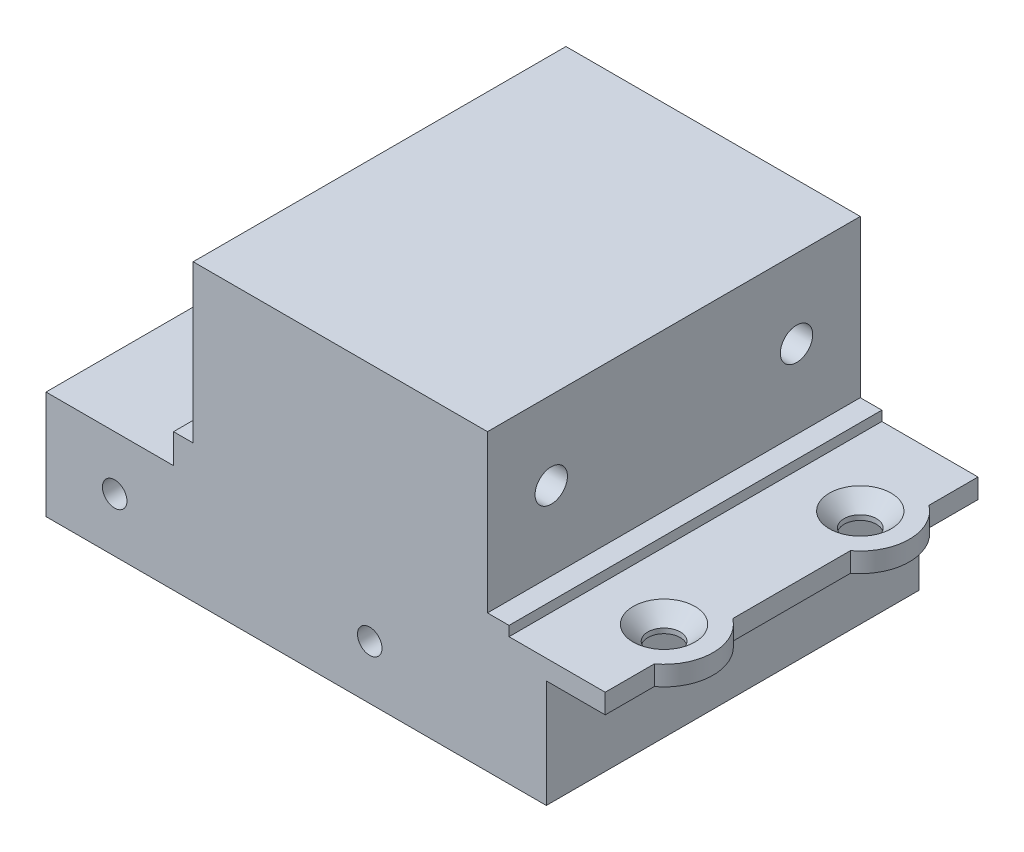
SolidWorks part; units mm, degrees
ref_plane "Спереди" through (0, 0, 0) normal (0, 0, 1) x (1, 0, 0)
ref_plane "Сверху" through (0, 0, 0) normal (0, 1, 0) x (1, 0, 0)
ref_plane "Справа" through (0, 0, 0) normal (1, 0, 0) x (0, 0, -1)
sketch "Эскиз6" [suppressed] plane through (0, 0, 0) normal (0, 1, 0) x (1, 0, 0)
  line L0 (-20, 0) -> (31, 0) construction
  line L1 (-20, -19) -> (31, -19)
  line L2 (-20, -19) -> (-20, 19)
  line L3 (-20, 19) -> (31, 19)
  line L4 (31, -19) -> (31, 19)
  line L5 (0, -19) -> (0, 19) construction
  dimension "D1" = 31
  dimension "D2" = 20
  dimension "D3" = 38
extrude "тело" [suppressed] add sketch "Эскиз6" along normal blind 11
sketch "Эскиз10" [suppressed] plane through (0, 11, 0) normal (0, 1, 0) x (1, 0, 0)
  circle A0 centre (0, 0) radius 10
  dimension "D1" = 20
extrude "основание оси" [suppressed] add sketch "Эскиз10" along normal blind 3
fillet "Скругление1" [suppressed] radius 3
sketch "Эскиз13" [suppressed] plane through (0, 0, 19) normal (0, 0, 1) x (1, 0, 0)
  line L0 (31, 5.5) -> (-13, 5.5) construction
  line L1 (31, 11) -> (31, 0) construction
  line L2 (0, 0) -> (0, 11) construction
  line L3 (-20, 11) -> (31, 11) construction
  circle A0 centre (-13, 5.5) radius 1.25
  circle A1 centre (13, 5.5) radius 1.25
  dimension "D1" = 2.5
  dimension "D2" = 26
  dimension "D3" = 18
extrude "отверстия под шурупы" [suppressed] cut sketch "Эскиз13" against normal through all
sketch "Эскиз15" [suppressed] plane through (0, 14, 0) normal (0, 1, 0) x (1, 0, 0)
  circle A0 centre (0, 0) radius 8.65
  dimension "D1" = 17.3
extrude "ось" [suppressed] add sketch "Эскиз15" along normal blind 13
sketch "Эскиз16" [suppressed] plane through (0, 27, 0) normal (0, 1, 0) x (1, 0, 0)
  line L0 (-7, 1.65) -> (-8.4912, 1.65) construction
  line L1 (-7, -1.65) -> (-8.4912, -1.65) construction
  line L2 (-1.65, 7) -> (-1.65, 8.4912)
  line L3 (1.65, 7) -> (1.65, 8.4912)
  line L4 (7, 1.65) -> (8.4912, 1.65) construction
  line L5 (7, -1.65) -> (8.4912, -1.65) construction
  line L6 (1.65, -7) -> (1.65, -8.4912)
  line L8 (-1.65, -7) -> (-1.65, -8.4912)
  circle A0 centre (0, 0) radius 7 construction
  arc A1 (-1.65, 7) -> (1.65, 7) centre (0, 7) ccw
  arc A2 (7, 1.65) -> (7, -1.65) centre (7, 0) ccw construction
  arc A3 (1.65, -7) -> (-1.65, -7) centre (0, -7) ccw
  arc A4 (-7, -1.65) -> (-7, 1.65) centre (-7, 0) ccw construction
  arc A5 (-8.4912, 1.65) -> (-8.4912, -1.65) centre (0, 0) ccw construction
  circle A6 centre (0, 0) radius 8.65 construction
  arc A7 (1.65, 8.4912) -> (-1.65, 8.4912) centre (0, 0) ccw
  arc A8 (8.4912, -1.65) -> (8.4912, 1.65) centre (0, 0) ccw construction
  arc A9 (-1.65, -8.4912) -> (1.65, -8.4912) centre (0, 0) ccw
  dimension "D1" = 14
  dimension "D2" = 1.65
extrude "крепление к серве" [suppressed] cut sketch "Эскиз16" against normal up to surface (13 mm away)
sketch "Эскиз26" [suppressed] plane through (0, 14, 0) normal (0, 1, 0) x (1, 0, 0)
  circle A0 centre (0, 7) radius 1.65
  circle A1 centre (0, -7) radius 1.65
  arc A2 (1.65, -7) -> (-1.65, -7) centre (0, -7) ccw construction
extrude "продолжение креплений" [suppressed] cut sketch "Эскиз26" against normal through all
chamfer "Фаска7" [suppressed] distance 2 angle 45
sketch "Эскиз17" [suppressed] plane through (0, 27, 0) normal (0, 1, 0) x (1, 0, 0)
  circle A0 centre (0, 0) radius 3
  dimension "D1" = 6
extrude "отверстие под болтик" [suppressed] cut sketch "Эскиз17" against normal through all
sketch "Эскиз24" [suppressed] plane through (0, 11, 0) normal (0, 1, 0) x (1, 0, 0)
  line L0 (31, 19) -> (-20, 19) construction
  line L1 (-15, 19) -> (15, 19)
  line L2 (-15, 19) -> (-15, -19)
  line L3 (-15, -19) -> (15, -19)
  line L4 (15, 19) -> (15, -19)
  line L5 (-20, -19) -> (31, -19) construction
  line L6 (0, 19) -> (0, -19) construction
  dimension "D1" = 30
extrude "крепление к арке" [suppressed] add sketch "Эскиз24" along normal blind 15
sketch "Эскиз27" [suppressed] plane through (-15, 0, 0) normal (-1, 0, 0) x (0, 0, 1)
  line L0 (0, 11) -> (0, 26) construction
  line L1 (-19, 11) -> (19, 11) construction
  line L2 (-19, 26) -> (19, 26) construction
  line L3 (-12.5, 18.5) -> (12.5, 18.5) construction
  circle A0 centre (-12.5, 18.5) radius 1.65
  circle A1 centre (12.5, 18.5) radius 1.65
  dimension "D2" = 3.3
  dimension "D1" = 25
  dimension "D3" = 7.5
extrude "отверстия под болты" [suppressed] cut sketch "Эскиз27" against normal through all
sketch "Эскиз19" [suppressed] plane through (0, 11, 0) normal (0, 1, 0) x (1, 0, 0)
  line L0 (15, -19) -> (31, -19) construction
  line L1 (37, 19) -> (23, 19)
  line L2 (37, 19) -> (37, -19)
  line L3 (37, -19) -> (23, -19)
  line L4 (23, 19) -> (23, -19)
  line L5 (31, 19) -> (31, -19) construction
  line L6 (31, -19) -> (31, 19) construction
  dimension "D1" = 6
  dimension "D2" = 8
extrude "выступ прикрутиться к колену" [suppressed] add sketch "Эскиз19" along normal blind 2
sketch "Эскиз20" [suppressed] plane through (0, 13, 0) normal (0, 1, 0) x (1, 0, 0)
  line L0 (34, 19) -> (34, -19) construction
  line L1 (37, 19) -> (23, 19) construction
  line L2 (23, -19) -> (37, -19) construction
  line L3 (37, -19) -> (37, 19) construction
  line L4 (23, 0) -> (37, 0) construction
  line L5 (23, 19) -> (23, -19) construction
  circle A0 centre (34, 10) radius 1.65
  circle A1 centre (34, -10) radius 1.65
  dimension "D3" = 3.3
  dimension "D1" = 3
  dimension "D2" = 20
extrude "шурупы сверху" [suppressed] cut sketch "Эскиз20" against normal through all
sketch "Эскиз23" [suppressed] plane through (0, 13, 0) normal (0, 1, 0) x (1, 0, 0)
  circle A0 centre (34, 10) radius 5
  circle A1 centre (34, -10) radius 5
  circle A2 centre (34, 10) radius 1.65
  circle A3 centre (34, -10) radius 1.65
  circle A4 centre (34, -10) radius 1.65 construction
  circle A5 centre (34, 10) radius 1.65 construction
  dimension "D1" = 10
extrude "наплывы" [suppressed] add sketch "Эскиз23" against normal up to surface (2 mm away)
chamfer "Фаска4" [suppressed] distance 1 angle 45
fillet "Скругление7" [suppressed] radius 3
chamfer "Фаска6" [suppressed] distance 1.5 angle 45
fillet "Скругление8" [suppressed] radius 0.5
sketch "Эскиз28" plane through (0, 0, 0) normal (0, 0, 1) x (1, 0, 0)
  line L0 (25.5, 0) -> (25.5, 11)
  line L1 (25.5, 11) -> (31.5, 11)
  line L2 (31.5, 11) -> (31.5, 13)
  line L3 (31.5, 13) -> (21.7, 13)
  line L5 (21.7, 14) -> (19.5, 14)
  line L6 (19.5, 14) -> (19.5, 30)
  line L7 (19.5, 30) -> (-10.5, 30)
  line L8 (-10.5, 30) -> (-10.5, 14)
  line L9 (-12.5, 11) -> (-25.5, 11)
  line L10 (-25.5, 11) -> (-25.5, 0)
  line L11 (-25.5, 0) -> (25.5, 0)
  line L12 (21.7, 13) -> (21.7, 14)
  line L13 (-12.5, 11) -> (-12.5, 14)
  line L14 (-12.5, 14) -> (-10.5, 14)
  circle A1 centre (7.5, 5.5) radius 1.25
  circle A2 centre (-18.5, 5.5) radius 1.25
  point P15 (0, 0)
  dimension "D6" = 11
  dimension "D9" = 2.5
  dimension "D2" = 30
  dimension "D3" = 6
  dimension "D4" = 51
  dimension "D5" = 2
  dimension "D7" = 14
  dimension "D8" = 26
  dimension "D10" = 5.5
  dimension "D11" = 6
  dimension "D12" = 2.2
  dimension "D13" = 18
  dimension "D14" = 16
  dimension "D15" = 3
  dimension "D16" = 2
extrude "Основа" add sketch "Эскиз28" along normal blind 38
sketch "Эскиз29" plane through (-10.5, 0, 0) normal (-1, 0, 0) x (0, 0, 1)
  line L0 (38, 30) -> (0, 30) construction
  line L1 (6.5, 22) -> (31.5, 22) construction
  line L2 (0, 30) -> (0, 14) construction
  circle A0 centre (6.5, 22) radius 1.65
  circle A1 centre (31.5, 22) radius 1.65
  point P4 (19, 22)
  point P5 (19, 30)
  point P8 (0, 0)
  point P11 (0, 22)
  dimension "D1" = 3.3
  dimension "D3" = 25
extrude "Отверстия под болты крепления к арке" cut sketch "Эскиз29" against normal up to next
sketch "Эскиз30" plane through (0, 13, 0) normal (0, 1, 0) x (1, 0, 0)
  line L0 (31.5, -38) -> (31.5, 0) construction
  line L1 (28.5, -29) -> (28.5, -9) construction
  circle A0 centre (28.5, -9) radius 1.65
  circle A1 centre (28.5, -29) radius 1.65
  point P4 (28.5, -19)
  point P7 (31.5, -19)
  dimension "D2" = 3.3
  dimension "D1" = 20
  dimension "D3" = 3
extrude "Отверстия под шурупы сверху" cut sketch "Эскиз30" against normal up to next
sketch "Эскиз31" plane through (0, 13, 0) normal (0, 1, 0) x (1, 0, 0)
  line L0 (31.5, -5) -> (31.5, -13)
  line L1 (31.5, -33) -> (31.5, -25)
  line L2 (31.5, -38) -> (31.5, 0) construction
  arc A0 (31.5, -13) -> (31.5, -5) centre (28.5, -9) ccw
  arc A1 (31.5, -33) -> (31.5, -25) centre (28.5, -29) ccw
  dimension "D1" = 10
extrude "Наплывы под шурупы сверху" add sketch "Эскиз31" against normal up to surface (2 mm away) up to face at (28.5, 11, 10.65)
chamfer "Фаска8" distance 1.5 angle 45 2 edges at (26.85, 13, 29) (26.85, 13, 9)
fillet "Скругление9" [suppressed] radius 2.7
fillet "Скругление10" [suppressed] radius 10
